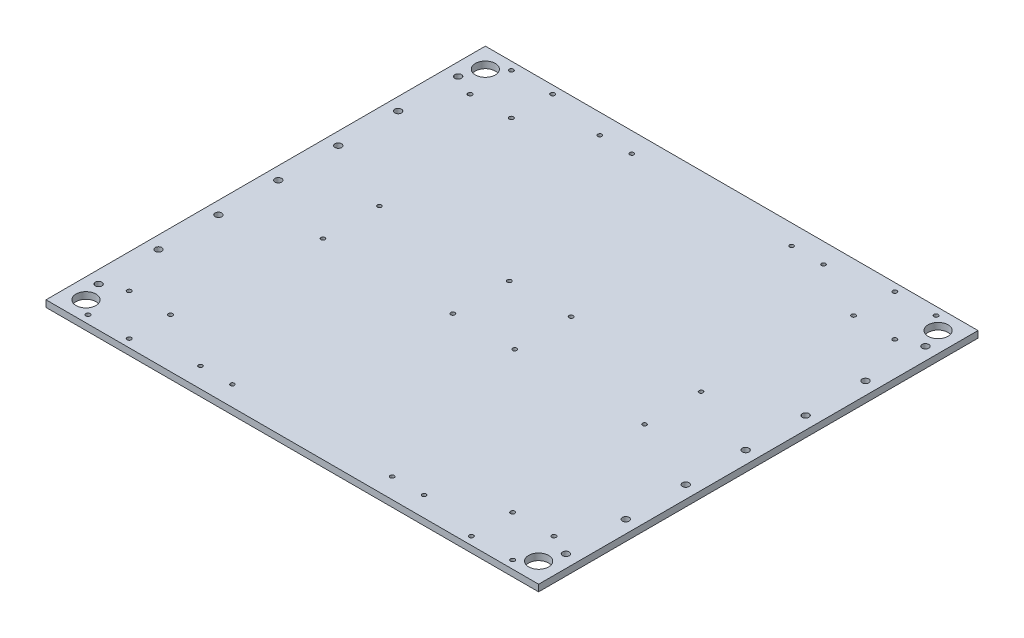
SolidWorks part; units mm, degrees
ref_plane "前视基准面" through (0, 0, 0) normal (0, 0, 1) x (1, 0, 0)
ref_plane "上视基准面" through (0, 0, 0) normal (0, 1, 0) x (1, 0, 0)
ref_plane "右视基准面" through (0, 0, 0) normal (1, 0, 0) x (0, 0, -1)
other "Configuration Table"
sketch "草图1" plane through (0, 0, 0) normal (0, 1, 0) x (1, 0, 0)
  line L1 (185, -165) -> (-185, -165)
  line L2 (185, -165) -> (185, 165)
  line L3 (185, 165) -> (-185, 165)
  line L4 (-185, -165) -> (-185, 165)
  line L5 (185, -165) -> (-185, 165) construction
  line L6 (185, 165) -> (-185, -165) construction
  point P0 (0, 0)
  dimension "D1" = 370
  dimension "D2" = 330
extrude "凸台-拉伸1" add sketch "草图1" along normal blind 5
sketch "草图2" plane through (0, 5, 0) normal (0, 1, 0) x (1, 0, 0)
  circle A0 centre (-159.5, 159) radius 1.6
  circle A1 centre (-128.5, 159) radius 1.6
  circle A2 centre (-159.5, 128) radius 1.6022
  circle A3 centre (-128.5, 128) radius 1.6
  circle A4 centre (128.5, 159) radius 1.6
  circle A5 centre (159.5, 159) radius 1.6
  circle A6 centre (128.5, 128) radius 1.6
  circle A7 centre (159.5, 128) radius 1.6
  circle A8 centre (128.5, -128) radius 1.6
  circle A9 centre (159.5, -128) radius 1.6
  circle A10 centre (159.5, -159) radius 1.6
  circle A11 centre (128.5, -159) radius 1.6
  circle A12 centre (-128.5, -159) radius 1.6
  circle A13 centre (-159.5, -159) radius 1.6
  circle A14 centre (-159.5, -128) radius 1.6
  circle A15 centre (-128.5, -128) radius 1.6
extrude "切除-拉伸1" cut sketch "草图2" against normal through all
sketch "草图3" plane through (0, 5, 0) normal (0, 1, 0) x (1, 0, 0)
  line L0 (-110, 60) -> (-110, 40)
  line L1 (110, -110) -> (-110, -110) construction
  line L2 (110, -110) -> (110, 110) construction
  line L3 (110, 110) -> (-110, 110) construction
  line L4 (-110, -110) -> (-110, 110) construction
  line L5 (110, -110) -> (-110, 110) construction
  line L6 (110, 110) -> (-110, -110) construction
  line L7 (-110, 110) -> (110, 110)
  line L8 (-110, 110) -> (-110, 90)
  line L9 (-110, 90) -> (110, 90)
  line L10 (110, 110) -> (110, 90)
  line L11 (-110, 60) -> (110, 60)
  line L12 (110, 60) -> (110, 40)
  line L13 (-110, 40) -> (110, 40)
  line L14 (-110, 10) -> (-110, -10)
  line L15 (-110, 10) -> (110, 10)
  line L16 (110, 10) -> (110, -10)
  line L17 (-110, -10) -> (110, -10)
  line L18 (-110, -40) -> (-110, -60)
  line L19 (-110, -40) -> (110, -40)
  line L20 (110, -40) -> (110, -60)
  line L21 (-110, -60) -> (110, -60)
  line L22 (-110, -90) -> (-110, -110)
  line L23 (-110, -90) -> (110, -90)
  line L24 (110, -90) -> (110, -110)
  line L25 (-110, -110) -> (110, -110)
  point P0 (0, 0)
  dimension "D1" = 220
  dimension "D2" = 220
  dimension "D3" = 20
  dimension "D4" = 5
extrude "切除-拉伸2" cut sketch "草图3" against normal through all contours L10 L7 L8 L9 | L0 L13 L12 L11 | L14 L17 L16 L15 | L18 L21 L20 L19 | L22 L25 L24 L23 | L8 L7 L10 L9 | L0 L13 L12 L11 region at (0, 5, -50) region at (0, 5, -100) region at (0, 5, 0) region at (0, 5, 50) region at (0, 5, 100)
sketch "草图8" plane through (0, 5, 0) normal (0, 1, 0) x (1, 0, 0)
  line L0 (120, 0) -> (-120, 0)
  line L1 (0, -120) -> (0, 120)
  point P4 (0, 0)
  point P8 (0, 0)
sketch "草图9" plane through (0, 5, 0) normal (0, 1, 0) x (1, 0, 0)
  line L1 (-117.6798, 117.0824) -> (121.8613, 117.0824)
  line L2 (-117.6798, 117.0824) -> (-117.6798, -116.4851)
  line L3 (-117.6798, -116.4851) -> (121.8613, -116.4851)
  line L4 (121.8613, 117.0824) -> (121.8613, -116.4851)
extrude "凸台-拉伸2" add sketch "草图9" against normal blind 5
sketch "草图12" plane through (0, 5, 0) normal (0, 1, 0) x (1, 0, 0)
  line L0 (185, 0) -> (175.5, 0) construction
  line L1 (185, -165) -> (185, 165) construction
  line L2 (0, -120) -> (0, 120) construction
  line L3 (120, 0) -> (-120, 0) construction
  line L4 (0, -120) -> (0, 120)
  line L5 (120, 0) -> (-120, 0)
  line L6 (-185, 0) -> (-175.5, 0) construction
  circle A0 centre (175.5, 0) radius 2.5
  circle A1 centre (175.5, 45) radius 2.5
  circle A2 centre (175.5, 90) radius 2.5
  circle A3 centre (175.5, 135) radius 2.5
  circle A4 centre (175.5, -135) radius 2.5
  circle A5 centre (175.5, -90) radius 2.5
  circle A6 centre (175.5, -45) radius 2.5
  circle A7 centre (-175.5, -45) radius 2.5
  circle A8 centre (-175.5, -90) radius 2.5
  circle A9 centre (-175.5, -135) radius 2.5
  circle A10 centre (-175.5, 135) radius 2.5
  circle A11 centre (-175.5, 90) radius 2.5
  circle A12 centre (-175.5, 45) radius 2.5
  circle A13 centre (-175.5, 0) radius 2.5
  dimension "D2" = 5
  dimension "D1" = 9.5
  dimension "D3" = 4
extrude "切除-拉伸6" cut sketch "草图12" against normal blind 10 contours A9 | A8 | A7 | A13 | A12 | A11 | A10 | A4 | A5 | A6 | A0 | A1 | A2 | A3 region at (175.5, 5, 0) region at (175.5, 5, -45) region at (175.5, 5, -90) region at (175.5, 5, -135) region at (175.5, 5, 135) region at (175.5, 5, 90) region at (175.5, 5, 45) region at (-175.5, 5, 45) region at (-175.5, 5, 90) region at (-175.5, 5, 135) region at (-175.5, 5, -135) region at (-175.5, 5, -90) region at (-175.5, 5, -45) region at (-175.5, 5, 0)
sketch "草图13" plane through (0, 5, 0) normal (0, 1, 0) x (1, 0, 0)
  line L0 (120, 0) -> (-120, 0) construction
  line L1 (-185, -165) -> (-170, -165)
  line L2 (-185, -165) -> (-185, -150)
  line L3 (-185, -150) -> (-170, -150)
  line L4 (-170, -165) -> (-170, -150)
  line L5 (0, -120) -> (0, 120) construction
  line L6 (120, 0) -> (-120, 0)
  line L7 (0, -120) -> (0, 120)
  circle A1 centre (-170, -150) radius 7.5
  circle A2 centre (170, -150) radius 7.5
  circle A3 centre (170, 150) radius 7.5
  circle A4 centre (-170, 150) radius 7.5
  dimension "D3" = 15
  dimension "D1" = 15
  dimension "D2" = 15
extrude "切除-拉伸7" cut sketch "草图13" against normal blind 10 contours A2 | L4 A1 L3 | L3 A1 L4 | A4 | A3 region at (-173.1831, 5, 153.1831) region at (-168.939, 5, 148.939) region at (170, 5, 150) region at (170, 5, -150) region at (-170, 5, -150)
sketch "草图14" plane through (0, 5, 0) normal (0, 1, 0) x (1, 0, 0)
  line L0 (-77.3344, 165) -> (-77.3344, 155) construction
  line L1 (185, 165) -> (-185, 165) construction
  line L2 (-185, 165) -> (-185, -165) construction
  line L3 (-185, 140) -> (-142, 140) construction
  line L4 (-108.7902, 140) -> (-29.7478, 140) construction
  line L5 (-142, 140) -> (-142, 94.5665) construction
  line L6 (-142, 140) -> (-2, 140)
  line L7 (-142, 140) -> (-142, 0)
  line L8 (-142, 0) -> (-2, 0)
  line L9 (-2, 140) -> (-2, 0)
  line L10 (-142, 140) -> (-84, 140) construction
  line L11 (-84, 140) -> (-84, 150) construction
  line L12 (-142, 140) -> (-2, 0) construction
  line L13 (-2, 140) -> (-142, 0) construction
  line L14 (120, 0) -> (-120, 0) construction
  line L15 (0, -120) -> (0, 120) construction
  line L16 (120, 0) -> (-120, 0)
  line L17 (0, -120) -> (0, 120)
  circle A0 centre (-84, 150) radius 1.505
  circle A1 centre (-60, 150) radius 1.505
  circle A2 centre (-120.7868, 21.2132) radius 1.505
  circle A3 centre (-23.2132, 21.2132) radius 1.55
  circle A4 centre (23.2132, 21.2132) radius 1.55
  circle A5 centre (120.7868, 21.2132) radius 1.505
  circle A6 centre (84, 150) radius 1.505
  circle A7 centre (60, 150) radius 1.505
  circle A8 centre (84, -150) radius 1.505
  circle A9 centre (60, -150) radius 1.505
  circle A10 centre (120.7868, -21.2132) radius 1.505
  circle A11 centre (23.2132, -21.2132) radius 1.55
  circle A12 centre (-23.2132, -21.2132) radius 1.55
  circle A13 centre (-120.7868, -21.2132) radius 1.505
  circle A14 centre (-84, -150) radius 1.505
  circle A15 centre (-60, -150) radius 1.505
  point P48 (-60, -150)
  point P53 (0, 0)
  dimension "D8" = 3.01
  dimension "D9" = 3.01
  dimension "D11" = 3.01
  dimension "D12" = 3.1
  dimension "D1" = 10
  dimension "D2" = 43
  dimension "D3" = 15
  dimension "D4" = 140
  dimension "D5" = 140
  dimension "D6" = 58
  dimension "D7" = 10
  dimension "D10" = 24
  dimension "D13" = 30
  dimension "D14" = 30
extrude "切除-拉伸8" cut sketch "草图14" against normal blind 10 contours A0 | A1 | A13 | A2 | A3 | A4 | A10 | A5 | A7 | A6 | A14 | A15 | A9 | A8 | A12 | A11 region at (-84, 5, -150) region at (-60, 5, -150) region at (-120.7868, 5, -21.2132) region at (-23.2132, 5, -21.2132) region at (23.2132, 5, -21.2132) region at (120.7868, 5, -21.2132) region at (84, 5, -150) region at (60, 5, -150) region at (84, 5, 150) region at (60, 5, 150) region at (120.7868, 5, 21.2132) region at (-120.7868, 5, 21.2132) region at (-84, 5, 150) region at (-60, 5, 150)
